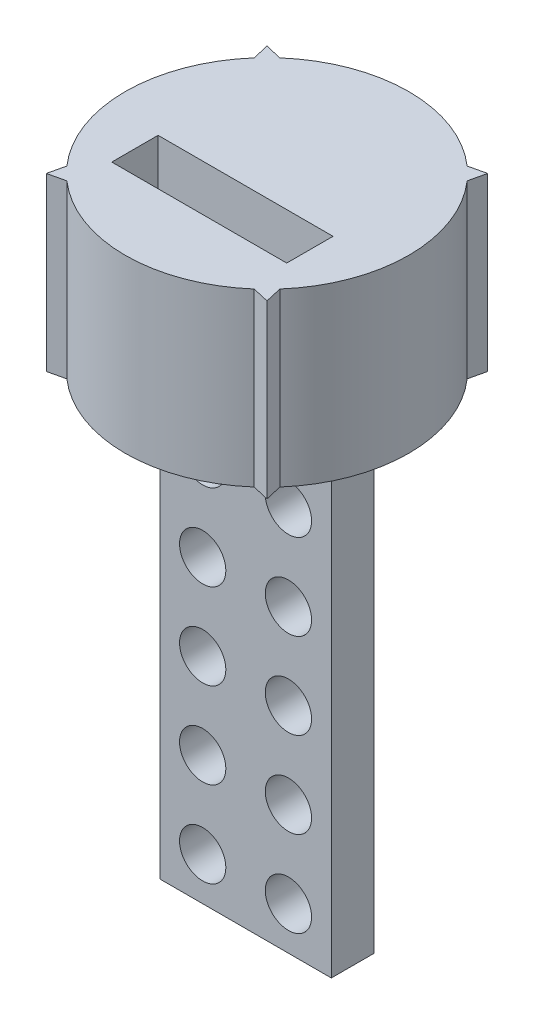
SolidWorks part; units mm, degrees
ref_plane "Front Plane" through (0, 0, 0) normal (0, 0, 1) x (1, 0, 0)
ref_plane "Top Plane" through (0, 0, 0) normal (0, 1, 0) x (1, 0, 0)
ref_plane "Right Plane" through (0, 0, 0) normal (1, 0, 0) x (0, 0, -1)
sketch "Sketch1" plane through (0, 0, 0) normal (0, 1, 0) x (1, 0, 0)
  line L0 (13.8701, 15.7677) -> (16.3439, 16.3439)
  line L1 (16.3439, 16.3439) -> (15.7677, 13.8701)
  line L2 (15.7677, -13.8701) -> (16.3439, -16.3439)
  line L3 (16.3439, -16.3439) -> (13.8701, -15.7677)
  line L4 (-13.8701, -15.7677) -> (-16.3439, -16.3439)
  line L5 (-16.3439, -16.3439) -> (-15.7677, -13.8701)
  line L6 (-15.7677, 13.8701) -> (-16.3439, 16.3439)
  line L7 (-16.3439, 16.3439) -> (-13.8701, 15.7677)
  line L8 (16.3439, 16.3439) -> (0, 0) construction
  line L9 (0, 0) -> (21, 0) construction
  arc A0 (13.8701, 15.7677) -> (-13.8701, 15.7677) centre (0, 0) ccw
  arc A1 (15.7677, -13.8701) -> (15.7677, 13.8701) centre (0, 0) ccw
  arc A2 (-13.8701, -15.7677) -> (13.8701, -15.7677) centre (0, 0) ccw
  arc A3 (-15.7677, 13.8701) -> (-15.7677, -13.8701) centre (0, 0) ccw
  point P18 (0, 0)
  dimension "D1" = 42
  dimension "D2" = 2.54
  dimension "D3" = 2.54
  dimension "D5" = 23.1137
  dimension "D6" = 45
  dimension "D4" = 4
extrude "Boss-Extrude1" add sketch "Sketch1" along normal blind 25.4
sketch "Sketch3" plane through (0, 0, 0) normal (0, 0, 1) x (1, 0, 0)
  line L0 (-21, 0) -> (-15.7677, 0) construction
  line L1 (-12.7, 0) -> (12.7, 0)
  line L2 (-12.7, 0) -> (-12.7, -69.85)
  line L3 (-12.7, -69.85) -> (12.7, -69.85)
  line L4 (12.7, 0) -> (12.7, -69.85)
  circle A0 centre (-6.35, -12.7) radius 3.429
  circle A1 centre (6.35, -12.7) radius 3.429
  circle A3 centre (6.35, -25.4) radius 3.429
  circle A5 centre (6.35, -38.1) radius 3.429
  circle A7 centre (6.35, -50.8) radius 3.429
  circle A9 centre (6.35, -63.5) radius 3.429
  circle A11 centre (-6.35, -25.4) radius 3.429
  circle A12 centre (-6.35, -38.1) radius 3.429
  circle A13 centre (-6.35, -50.8) radius 3.429
  circle A14 centre (-6.35, -63.5) radius 3.429
  circle A15 centre (19.05, -12.7) radius 3.429 [skipped]
  circle A16 centre (19.05, -25.4) radius 3.429 [skipped]
  circle A17 centre (19.05, -38.1) radius 3.429 [skipped]
  circle A18 centre (19.05, -50.8) radius 3.429 [skipped]
  circle A19 centre (19.05, -63.5) radius 3.429 [skipped]
  point P9 (0, 0)
  point P10 (0, 0)
  point P11 (0, 0)
  point P40 (0, 0)
  dimension "D3" = 6.858
  dimension "D7" = 12.7
  dimension "D1" = 25.4
  dimension "D4" = 6.35
  dimension "D5" = 3
  dimension "D6" = 5
extrude "Boss-Extrude3" add sketch "Sketch3" along normal mid plane 6.35
sketch "Sketch4" plane through (0, 0, 0) normal (0, -1, 0) x (-1, 0, 0)
  line L0 (12.7, -3.175) -> (-12.7, -3.175) construction
  line L1 (12.954, -3.175) -> (-12.954, -3.175)
  line L2 (12.954, -3.175) -> (12.954, -10.033)
  line L3 (12.954, -10.033) -> (-12.954, -10.033)
  line L4 (-12.954, -3.175) -> (-12.954, -10.033)
  line L5 (0, 0) -> (0, -21) construction
  line L6 (0, 0) -> (-12.7, 0) construction
  line L7 (-12.7, -3.175) -> (-12.7, 3.175) construction
  arc A0 (-13.8701, -15.7677) -> (13.8701, -15.7677) centre (0, 0) ccw construction
  point P12 (0, -10.033)
  dimension "D1" = 6.858
  dimension "D2" = 25.908
extrude "Cut-Extrude1" cut sketch "Sketch4" against normal through all
fillet "Fillet2" radius 5.08 3 edges at (-12.7, 0, 0) (12.7, 0, 0) (0, 0, -3.175)
